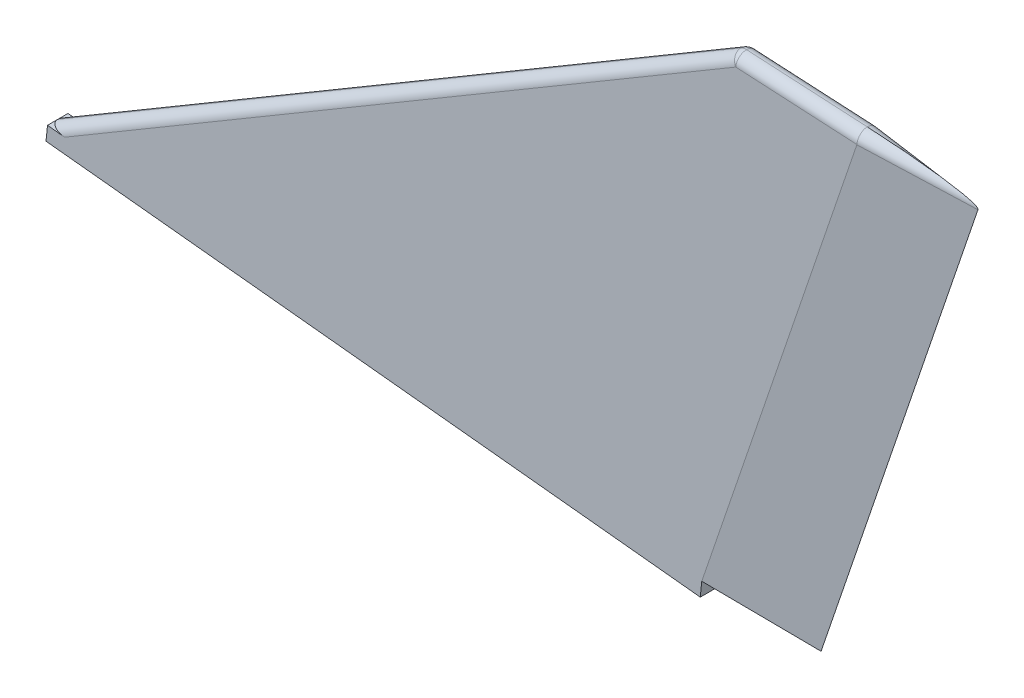
SolidWorks part; units mm, degrees
ref_plane "Front Plane" through (0, 0, 0) normal (0, 0, 1) x (1, 0, 0)
ref_plane "Top Plane" through (0, 0, 0) normal (0, 1, 0) x (1, 0, 0)
ref_plane "Right Plane" through (0, 0, 0) normal (1, 0, 0) x (0, 0, -1)
sketch "Sketch1" plane through (0, 0, 0) normal (0, 0, 1) x (1, 0, 0)
  line L1 (0, 0) -> (260.7069, -26.9874)
  line L2 (260.7069, -26.9874) -> (315.4921, 133.9429)
  line L3 (315.4921, 133.9429) -> (234.2089, 138.3024)
  line L4 (234.2089, 138.3024) -> (0, 0)
  dimension "D1" = 262.1
  dimension "D2" = 102.89
  dimension "D3" = 170
  dimension "D4" = 81.4
  dimension "D7" = 74.27
extrude "Boss-Extrude1" add sketch "Sketch1" along normal mid plane 7
ref_plane "Plane1" through (73.6278, 216.2803, 0) normal (0.3223, 0.9466, 0) x (0, 0, -1)
sketch "Sketch2" plane through (73.6278, 216.2803, 0) normal (0.3223, 0.9466, 0) x (0, 0, -1)
  line L0 (0, -255.4951) -> (-3.5, -218.9951)
  line L1 (-3.5, -255.4951) -> (3.5, -255.4951) construction
  line L2 (-3.5, -218.9951) -> (-3.5, -255.4951)
  line L3 (-3.5, -255.4951) -> (0, -255.4951)
  dimension "D1" = 36.5
extrude "Cut-Extrude1" cut sketch "Sketch2" against normal through all
sketch "Sketch9" plane through (73.6278, 216.2803, 0) normal (0.3223, 0.9466, 0) x (0, 0, -1)
  line L0 (0, -255.4951) -> (3.5, -218.9951)
  line L1 (0, -255.4951) -> (3.5, -255.4951) construction
  line L2 (3.5, -255.4951) -> (3.5, -177.1436) construction
  line L3 (3.5, -218.9951) -> (3.5, -255.4951)
  line L4 (3.5, -255.4951) -> (0, -255.4951)
  dimension "D1" = 36.5
extrude "Cut-Extrude4" cut sketch "Sketch9" against normal through all
fillet "Fillet3" radius 3.5 6 edges at (255.9176, 137.1381, 3.5) (255.9176, 137.1381, -3.5) (296.5592, 134.9584, -1.75) (296.5592, 134.9584, 1.75) (117.1044, 69.1512, 3.5) (117.1044, 69.1512, -3.5)
sketch "Sketch10" plane through (0, 0, 0) normal (-0.103, -0.9947, 0) x (0.9947, -0.103, 0)
  line L1 (224.6564, 3.5) -> (224.6564, -3.5)
  line L2 (224.6564, -3.5) -> (5.888, -3.5)
  line L3 (0, 0) -> (0, -3.5)
  line L5 (0, 0) -> (0, 3.5)
  line L6 (0, 3.5) -> (224.6564, 3.5)
  line L7 (0, -3.5) -> (5.888, -3.5)
extrude "Boss-Extrude2" add sketch "Sketch10" along normal blind 5
